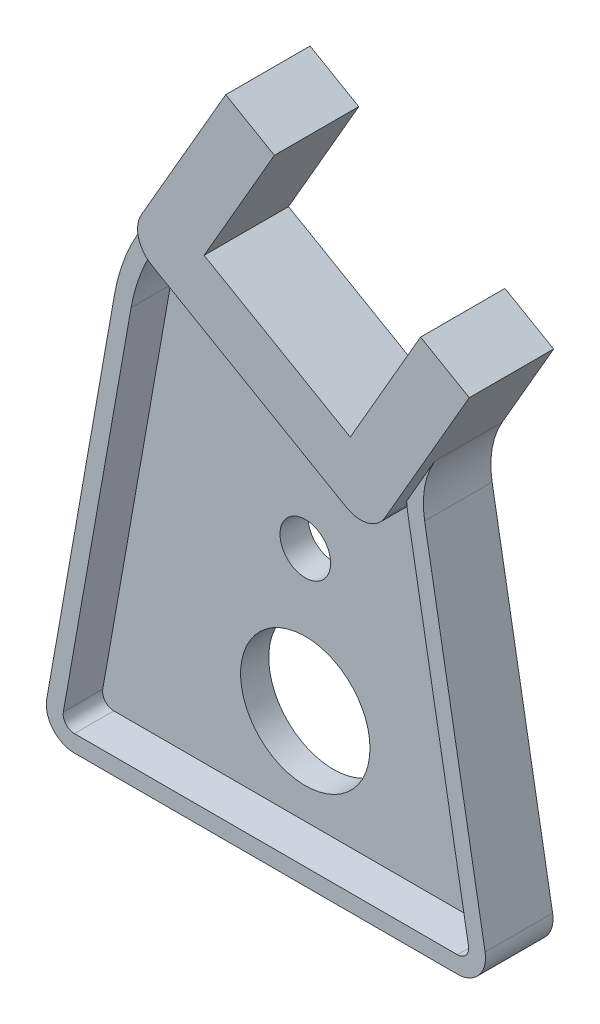
SolidWorks part; units mm, degrees
ref_plane "Front Plane" through (0, 0, 0) normal (0, 0, 1) x (1, 0, 0)
ref_plane "Top Plane" through (0, 0, 0) normal (0, 1, 0) x (1, 0, 0)
ref_plane "Right Plane" through (0, 0, 0) normal (1, 0, 0) x (0, 0, -1)
sketch "Sketch1" plane through (0, 0, 0) normal (0, 0, 1) x (1, 0, 0)
  line L0 (-34.0412, 0) -> (34.0412, 0)
  line L1 (38.9653, 5.8682) -> (28.213, 66.8476)
  line L2 (-38.9653, 5.8682) -> (-26.9273, 74.1391)
  line L3 (29.9947, 76.9523) -> (39.1506, 92.8109)
  line L4 (39.1506, 92.8109) -> (30.4904, 97.8109)
  line L5 (-4.1506, 117.8109) -> (-22.7699, 85.5614)
  line L6 (30.4904, 97.8109) -> (17.9904, 76.1603)
  line L7 (17.9904, 76.1603) -> (-7.9904, 91.1603)
  line L8 (-7.9904, 91.1603) -> (4.5096, 112.8109)
  line L9 (29.9947, 76.9523) -> (24.1506, 66.8301)
  line L10 (-17.3205, 85) -> (17.3205, 65)
  line L11 (0, 0) -> (0, 75) construction
  line L12 (0, 75) -> (39.8017, 143.9386) construction
  line L15 (-18.8438, 86.3615) -> (-20.1718, 84.0614)
  line L16 (-36.0108, 5.3473) -> (-23.9729, 73.6181)
  line L17 (-34.0412, 3) -> (34.0412, 3)
  line L18 (36.0108, 5.3473) -> (25.2585, 66.3267)
  line L19 (27.3966, 78.4523) -> (35.0526, 91.7128) construction
  line L20 (35.0526, 91.7128) -> (-3.0526, 113.7128) construction
  line L21 (4.5096, 112.8109) -> (-4.1506, 117.8109)
  line L22 (39.1506, 92.8109) -> (-4.1506, 117.8109) construction
  line L23 (-3.0526, 113.7128) -> (-20.1718, 84.0614) construction
  arc A0 (-26.9273, 74.1391) -> (-22.7699, 85.5614) centre (7.541, 68.0614) cw
  arc A1 (28.213, 66.8476) -> (29.9947, 76.9523) centre (42.9851, 69.4523) cw
  circle A2 centre (0, 20) radius 11.5
  circle A3 centre (0, 45) radius 4.5
  arc A4 (24.1506, 66.8301) -> (17.3205, 65) centre (19.8205, 69.3301) cw
  arc A5 (-19.1506, 91.8301) -> (-17.3205, 85) centre (-14.8205, 89.3301) ccw
  arc A6 (-34.0412, 0) -> (-38.9653, 5.8682) centre (-34.0412, 5) cw
  arc A7 (34.0412, 0) -> (38.9653, 5.8682) centre (34.0412, 5) ccw
  arc A8 (-23.9729, 73.6181) -> (-20.1718, 84.0614) centre (7.541, 68.0614) cw
  arc A9 (-34.0412, 3) -> (-36.0108, 5.3473) centre (-34.0412, 5) cw
  arc A10 (34.0412, 3) -> (36.0108, 5.3473) centre (34.0412, 5) ccw
  arc A11 (25.2585, 66.3267) -> (25.0198, 68.3355) centre (42.9851, 69.4523) cw
  arc A12 (25.2585, 66.3267) -> (27.3966, 78.4523) centre (42.9851, 69.4523) cw construction
  point P19 (-28.7082, 71.0937)
  point P26 (0, 0)
  point P32 (-40, 0)
  point P35 (40, 0)
  point P41 (17.5, 105.3109)
  dimension "D1" = 60
  dimension "D2" = 35
  dimension "D8" = 5
  dimension "D9" = 5
  dimension "D10" = 15
  dimension "D11" = 9
  dimension "D12" = 23
  dimension "D17" = 5
  dimension "D3" = 75
  dimension "D4" = 50
  dimension "D5" = 30
  dimension "D6" = 35
  dimension "D7" = 25
  dimension "D13" = 25
  dimension "D14" = 20
  dimension "D15" = 20
  dimension "D16" = 80
  dimension "D18" = 3
extrude "Boss-Extrude1" add sketch "Sketch1" along normal blind 12 contours A11 L18 A10 L17 A9 L16 A8 L15 A5 L5 A0 L2 A6 L0 A7 L1 A1 L9 region at (-36.9481, 2.5609, 0)
extrude "Boss-Extrude2" add sketch "Sketch1<3>" along normal blind 5 contours L18 A11 L9 A4 L10 A5 L15 A8 L16 A9 L17 A10 A2 A3 region at (-1.155, 38.2077, 0)
sketch "Sketch1<3>" plane through (0, 0, 0) normal (0, 0, 1) x (1, 0, 0) same geometry as "Sketch1"
extrude "Boss-Extrude3" add sketch "Sketch1<4>" along normal blind 15 contours L5 A5 L10 A4 L9 L3 L4 L6 L7 L8 L21 region at (26.8178, 73.042, 0)
sketch "Sketch1<4>" plane through (0, 0, 0) normal (0, 0, 1) x (1, 0, 0) same geometry as "Sketch1"
